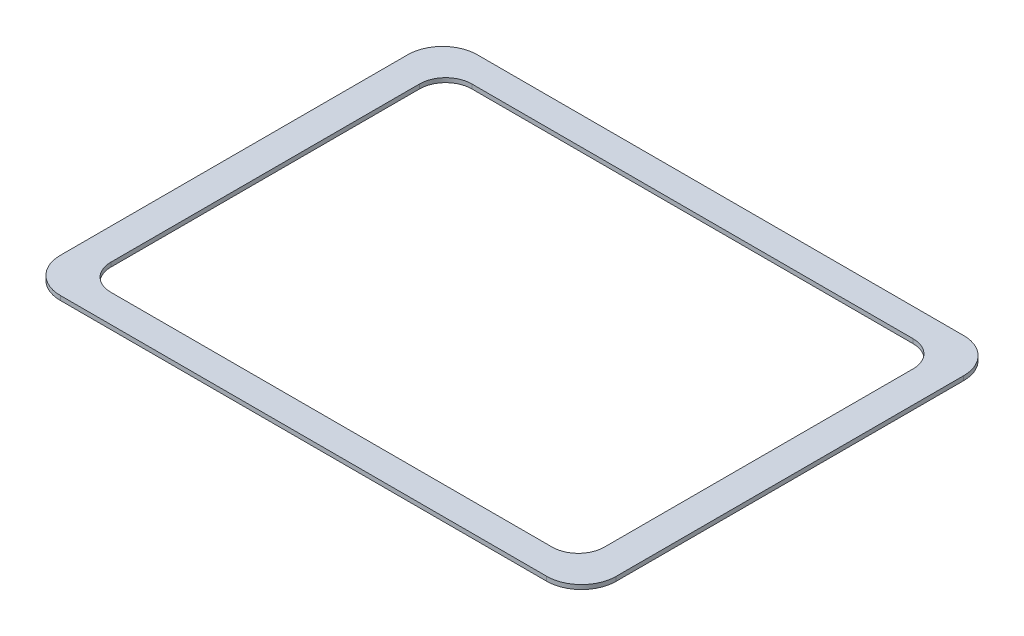
SolidWorks part; units mm, degrees
ref_plane "Front Plane" through (0, 0, 0) normal (0, 0, 1) x (1, 0, 0)
ref_plane "Top Plane" through (0, 0, 0) normal (0, 1, 0) x (1, 0, 0)
ref_plane "Right Plane" through (0, 0, 0) normal (1, 0, 0) x (0, 0, -1)
sketch "Sketch2" plane through (0, 49.0346, 0) normal (0, 1, 0) x (1, 0, 0)
  line L23 (74.7125, 99.3466) -> (-103.0875, 99.3466)
  line L24 (87.4125, -40.3534) -> (87.4125, 86.6466)
  line L26 (-94.8589, -42.8159) -> (66.4838, -42.8159)
  line L32 (-103.0875, -53.0534) -> (74.7125, -53.0534) construction
  line L33 (-115.7875, 86.6466) -> (-115.7875, -40.3534) construction
  line L34 (-103.0875, -53.0534) -> (74.7125, -53.0534)
  line L35 (-115.7875, 86.6466) -> (-115.7875, -40.3534)
  line L40 (76.0075, -33.2922) -> (76.0075, 79.5854)
  line L42 (-104.3826, 79.5854) -> (-104.3826, 23.1466)
  line L43 (-104.3826, 23.1466) -> (-104.3826, -33.2922)
  line L45 (76.0075, -33.2922) -> (76.0075, 79.5854)
  line L47 (-104.3826, 79.5854) -> (-104.3826, 23.1466)
  line L48 (-104.3826, 23.1466) -> (-104.3826, -33.2922)
  line L72 (-94.8589, -42.8159) -> (66.4838, -42.8159)
  line L74 (66.4838, 89.1092) -> (-94.8589, 89.1092)
  line L75 (66.4838, 89.1092) -> (-94.8589, 89.1092)
  arc A2 (87.4125, 86.6466) -> (74.7125, 99.3466) centre (74.7125, 86.6466) ccw
  arc A17 (-103.0875, 99.3466) -> (-115.7875, 86.6466) centre (-103.0875, 86.6466) ccw
  arc A21 (-104.3826, -33.2922) -> (-94.8589, -42.8159) centre (-94.8589, -33.2922) ccw
  arc A22 (-104.3826, -33.2922) -> (-94.8589, -42.8159) centre (-94.8589, -33.2922) ccw
  arc A23 (66.4838, -42.8159) -> (76.0075, -33.2922) centre (66.4838, -33.2922) ccw
  arc A24 (66.4838, -42.8159) -> (76.0075, -33.2922) centre (66.4838, -33.2922) ccw
  arc A25 (76.0075, 79.5854) -> (66.4838, 89.1092) centre (66.4838, 79.5854) ccw
  arc A26 (76.0075, 79.5854) -> (66.4838, 89.1092) centre (66.4838, 79.5854) ccw
  arc A27 (-94.8589, 89.1092) -> (-104.3826, 79.5854) centre (-94.8589, 79.5854) ccw
  arc A28 (-94.8589, 89.1092) -> (-104.3826, 79.5854) centre (-94.8589, 79.5854) ccw
  arc A29 (74.7125, -53.0534) -> (87.4125, -40.3534) centre (74.7125, -40.3534) ccw construction
  arc A30 (-115.7875, -40.3534) -> (-103.0875, -53.0534) centre (-103.0875, -40.3534) ccw construction
  arc A31 (74.7125, -53.0534) -> (87.4125, -40.3534) centre (74.7125, -40.3534) ccw
  arc A32 (-115.7875, -40.3534) -> (-103.0875, -53.0534) centre (-103.0875, -40.3534) ccw
  dimension "D1" = 1.5875
extrude "MainBody" add sketch "Sketch2" along normal blind 1.5875
equation "\"ClampDepth\"= 3 / 8in"
equation "\"D1@Sketch2\"=0.0625"
